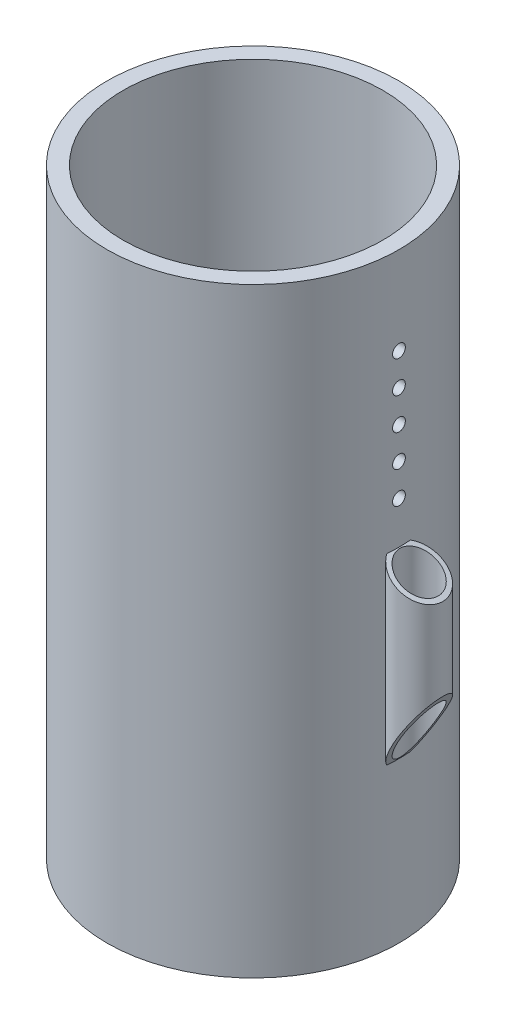
SolidWorks part; units mm, degrees
ref_plane "Front Plane" through (0, 0, 0) normal (0, 0, 1) x (1, 0, 0)
ref_plane "Top Plane" through (0, 0, 0) normal (0, 1, 0) x (1, 0, 0)
ref_plane "Right Plane" through (0, 0, 0) normal (1, 0, 0) x (0, 0, -1)
sketch "Sketch1" plane through (0, 0, 0) normal (0, 1, 0) x (1, 0, 0)
  circle A0 centre (0, 0) radius 11.43
  circle A1 centre (0, 0) radius 10.16
  dimension "D1" = 1.27
extrude "Boss-Extrude1" add sketch "Sketch1" along normal blind 46.99
sketch "Sketch3" plane through (0, 0, 0) normal (0, 1, 0) x (1, 0, 0)
  line L0 (0, 0) -> (13, 0) construction
  circle A0 centre (13, 0) radius 1.5
  circle A1 centre (13, 0) radius 1.85
  point P6 (0, 0)
  point P7 (0, 0)
extrude "Boss-Extrude2" add sketch "Sketch3" along normal blind 2.5 from offset 20
chamfer "Chamfer4" distance 7.5 angle 30 1 edges at (11.43, 20, 0)
chamfer "Chamfer5" distance 7.5 angle 30 1 edges at (11.43, 22.5, 0)
ref_plane "Plane2" through (11.43, 0, 0) normal (1, 0, 0) x (0, 0, -1)
sketch "Sketch4" plane through (11.43, 0, 0) normal (1, 0, 0) x (0, 0, -1)
  circle A0 centre (0, 30.1326) radius 0.5
  circle A1 centre (0, 32.6326) radius 0.5
  circle A2 centre (0, 35.1326) radius 0.5
  circle A3 centre (0, 37.6326) radius 0.5
  circle A4 centre (0, 40.1326) radius 0.5
  point P10 (0.2316, 40.1408)
  point P11 (0, 40.1326)
  dimension "D1" = 2.5
  dimension "D3" = 2.5
  dimension "D2" = 2.5
  dimension "D4" = 2.5
extrude "Cut-Extrude1" cut sketch "Sketch4" against normal blind 5
